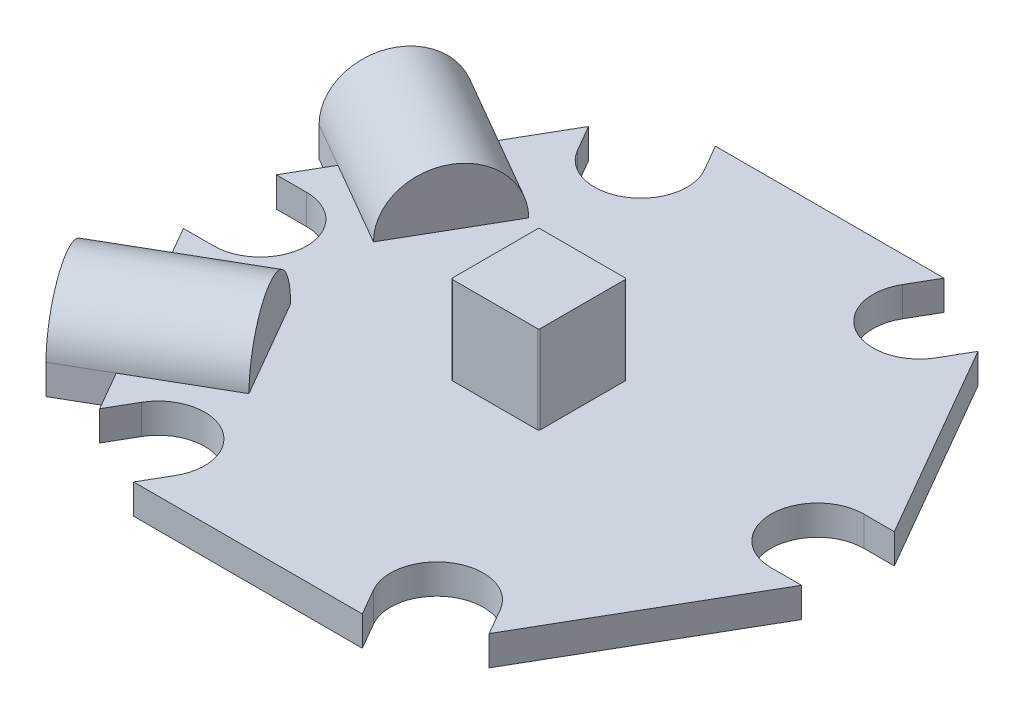
SolidWorks part; units mm, degrees
ref_plane "Front Plane" through (0, 0, 0) normal (0, 0, 1) x (1, 0, 0)
ref_plane "Top Plane" through (0, 0, 0) normal (0, 1, 0) x (1, 0, 0)
ref_plane "Right Plane" through (0, 0, 0) normal (1, 0, 0) x (0, 0, -1)
sketch "Sketch1" plane through (0, 0, 0) normal (0, 1, 0) x (1, 0, 0)
  line L7 (5.7412, 9.9441) -> (-5.7412, 9.9441)
  line L8 (-5.7412, 9.9441) -> (-11.4825, 0)
  line L9 (-11.4825, 0) -> (-5.7412, -9.9441)
  line L10 (-5.7412, -9.9441) -> (5.7412, -9.9441)
  line L11 (5.7412, -9.9441) -> (11.4825, 0)
  line L12 (11.4825, 0) -> (5.7412, 9.9441)
  circle A1 centre (0, 0) radius 9.9441 construction
extrude "Boss-Extrude1" add sketch "Sketch1" along normal blind 1.016
sketch "Sketch2" plane through (0, 1.016, 0) normal (0, 1, 0) x (1, 0, 0)
  line L6 (9.525, 1.5875) -> (13.1378, 1.5875)
  line L12 (9.525, -1.5875) -> (13.1378, -1.5875)
  line L13 (13.1378, 1.5875) -> (13.1378, -1.5875)
  arc A1 (9.525, 1.5875) -> (9.525, -1.5875) centre (9.525, 0) ccw
  dimension "D1" = 9.525
extrude "Cut-Extrude1" cut sketch "Sketch2" against normal blind 1.016
ref_axis "Axis1" through (0, 4.2168, 0) along (0, -1, 0)
pattern_circular "CirPattern1" count 6 every 60 about axis through (0, 4.2168, 0) along (0, -1, 0) of "Cut-Extrude1"
sketch "Sketch3" plane through (0, 1.016, 0) normal (0, 1, 0) x (1, 0, 0)
  line L1 (-1.5, -1.5) -> (-1.5, 1.5)
  line L2 (-1.5, -1.5) -> (1.5, -1.5)
  line L3 (-1.5, 1.5) -> (1.5, 1.5)
  line L4 (1.5, -1.5) -> (1.5, 1.5)
  line L6 (-1.5, 1.5) -> (-0.0012, 0.0012) construction
  point P9 (0, 0)
  dimension "D1" = 3
  dimension "D2" = 3
extrude "Boss-Extrude2" add sketch "Sketch3" along normal blind 3
fillet "Fillet1" radius 0.0508 1 edges at (1.5, 2.516, 1.5)
fillet "Fillet2" radius 0.0508 1 edges at (-1.5, 2.516, -1.5)
fillet "Fillet3" radius 0.0508 1 edges at (1.5, 2.516, -1.5)
fillet "Fillet4" radius 0.0508 1 edges at (-1.5, 2.516, 1.5)
sketch "Sketch4" plane through (0, 1.016, 0) normal (0, 1, 0) x (1, 0, 0)
  line L0 (-8.4528, -3.1242) -> (-6.5097, -6.4897)
  line L1 (-8.4528, -3.1242) -> (-6.4951, -1.9939)
  line L2 (-6.5097, -6.4897) -> (-4.552, -5.3594)
  line L3 (-6.4951, -1.9939) -> (-4.552, -5.3594)
  line L4 (-8.4528, -3.1242) -> (-4.552, -5.3594) construction
  line L5 (-6.5097, -6.4897) -> (-6.4951, -1.9939) construction
  line L11 (-1.5, 1.4492) -> (-1.5, -1.4492) construction
  point P1 (-6.5024, -4.2418)
  point P13 (-1.5, 0)
  dimension "D1" = 3.8862
  dimension "D2" = 2.2606
  dimension "D3" = 6.5024
  dimension "D4" = 4.2418
ref_plane "Plane1" through (-5.7347, 0, 3.3109) normal (-0.866, 0, 0.5) x (0.5, 0, 0.866)
sketch "Sketch5" plane through (-5.7347, 0, 3.3109) normal (-0.866, 0, 0.5) x (0.5, 0, 0.866)
  line L0 (-1.5208, 1.016) -> (2.3654, 1.016) construction
  line L1 (-1.5208, 1.016) -> (2.3654, 1.016)
  arc A0 (-1.5208, 1.016) -> (2.3654, 1.016) centre (0.4223, 1.016) cw
extrude "Boss-Extrude3" add sketch "Sketch5" along normal blind 5.08 contours A0 L1 region at (-5.5235, 1.8407, 3.6766)
pattern_circular "CirPattern2" count 2 every 60 about axis through (0, 4.2168, 0) along (0, -1, 0) of "Boss-Extrude3"
sketch "Sketch7" plane through (0, 1.016, 0) normal (0, -1, 0) x (1, 0, 0)
  line L4 (-10.8945, 4.5339) -> (-9.3722, 3.655)
  line L5 (-9.3722, 3.655) -> (-7.4291, 7.0206)
  line L6 (-7.4291, 7.0206) -> (-8.9514, 7.8994)
  line L7 (-8.9514, 7.8994) -> (-10.8945, 4.5339)
  line L8 (-10.8945, 4.5339) -> (-9.3722, 3.655)
  line L9 (-9.3722, 3.655) -> (-7.4291, 7.0206)
  line L10 (-7.4291, 7.0206) -> (-8.9514, 7.8994)
  line L11 (-8.9514, 7.8994) -> (-10.8945, 4.5339)
  dimension "D1" = 0
extrude "Boss-Extrude4" add sketch "Sketch7" along normal up to surface (1.016 mm away) up to face at (0, 0, 0)
sketch "Sketch8" plane through (0, 1.016, 0) normal (0, -1, 0) x (1, 0, 0)
  line L4 (-9.3737, -7.168) -> (-7.8514, -6.2891)
  line L5 (-7.8514, -6.2891) -> (-9.7945, -2.9235)
  line L6 (-9.7945, -2.9235) -> (-11.3168, -3.8024)
  line L7 (-11.3168, -3.8024) -> (-9.3737, -7.168)
  line L8 (-9.3737, -7.168) -> (-7.8514, -6.2891)
  line L9 (-7.8514, -6.2891) -> (-9.7945, -2.9235)
  line L10 (-9.7945, -2.9235) -> (-11.3168, -3.8024)
  line L11 (-11.3168, -3.8024) -> (-9.3737, -7.168)
  dimension "D1" = 0
extrude "Boss-Extrude5" add sketch "Sketch8" along normal up to surface (1.016 mm away) up to face at (-1.3088, 0, 0.8253)
